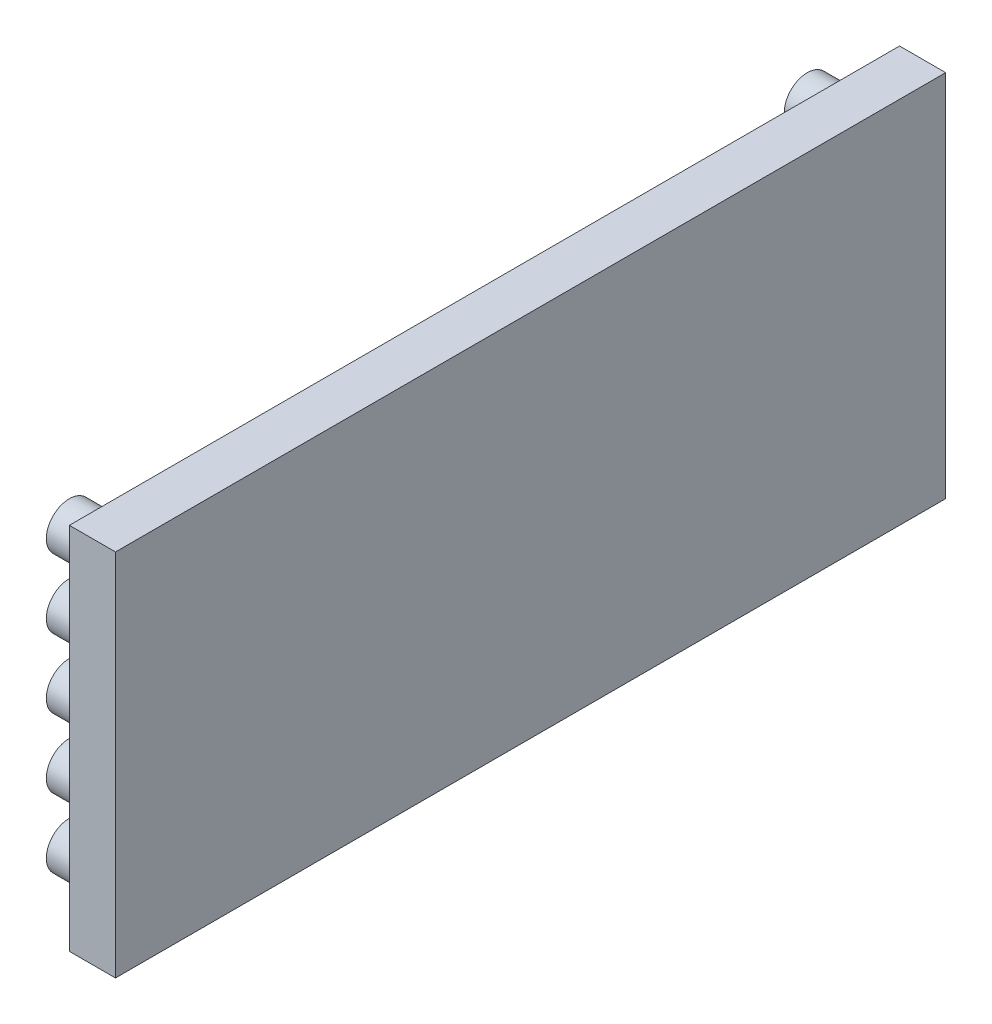
SolidWorks part; units mm, degrees
ref_plane "Front Plane" through (0, 0, 0) normal (0, 0, 1) x (1, 0, 0)
ref_plane "Top Plane" through (0, 0, 0) normal (0, 1, 0) x (1, 0, 0)
ref_plane "Right Plane" through (0, 0, 0) normal (1, 0, 0) x (0, 0, -1)
sketch "Sketch1" plane through (0, 0, 0) normal (1, 0, 0) x (0, 0, -1)
  line L1 (0, 0) -> (457.2, 0)
  line L2 (0, 0) -> (0, 203.2)
  line L3 (0, 203.2) -> (457.2, 203.2)
  line L4 (457.2, 0) -> (457.2, 203.2)
  dimension "D1" = 457.2
  dimension "D2" = 203.2
extrude "Boss-Extrude1" add sketch "Sketch1" along normal mid plane 25.4
sketch "Sketch2" plane through (-12.7, 0, 0) normal (-1, 0, 0) x (0, 0, 1)
  line L1 (-457.2, 203.2) -> (0, 203.2) construction
  line L2 (0, 203.2) -> (0, 0) construction
  circle A0 centre (-25.4, 177.8) radius 12.7
  circle A1 centre (-25.4, 139.7) radius 12.7
  circle A2 centre (-25.4, 101.6) radius 12.7
  circle A3 centre (-25.4, 63.5) radius 12.7
  circle A4 centre (-25.4, 25.4) radius 12.7
  circle A5 centre (-431.8, 139.7) radius 12.7
  circle A6 centre (-431.8, 101.6) radius 12.7
  circle A7 centre (-431.8, 63.5) radius 12.7
  circle A8 centre (-431.8, 25.4) radius 12.7
  circle A9 centre (-431.8, 177.8) radius 12.7
  dimension "D1" = 25.4
  dimension "D3" = 5
  dimension "D2" = 25.4
  dimension "D4" = 2
extrude "Boss-Extrude2" add sketch "Sketch2" along normal blind 25.4
